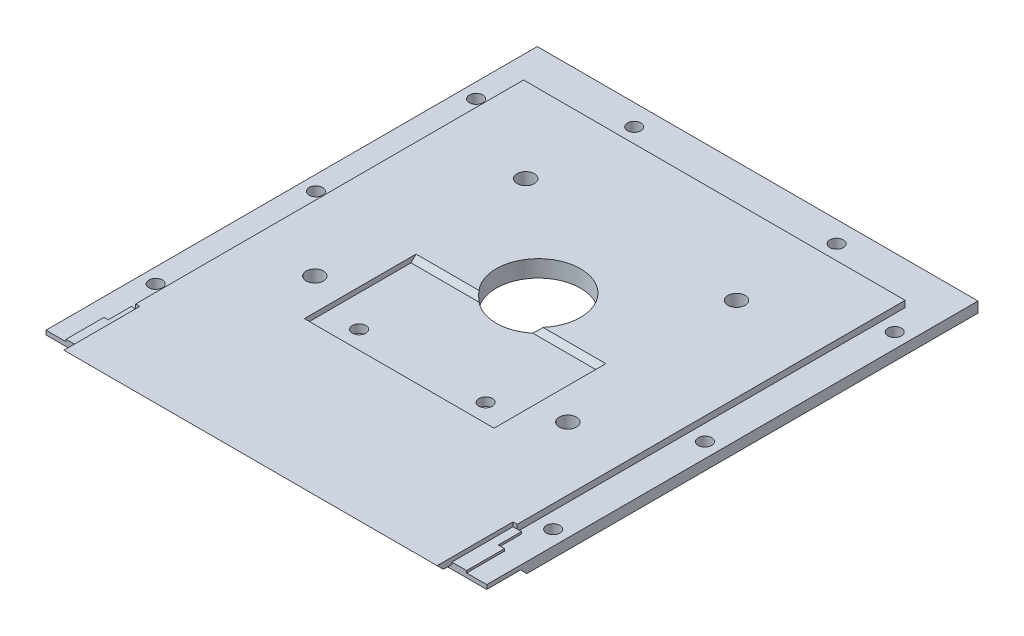
SolidWorks part; units mm, degrees
ref_plane "前视基准面" through (0, 0, 0) normal (0, 0, 1) x (1, 0, 0)
ref_plane "上视基准面" through (0, 0, 0) normal (0, 1, 0) x (1, 0, 0)
ref_plane "右视基准面" through (0, 0, 0) normal (1, 0, 0) x (0, 0, -1)
other "Configuration Table"
sketch "草图1" plane through (0, 0, 0) normal (0, 1, 0) x (1, 0, 0)
  line L1 (0, 0) -> (90.5, 0)
  line L2 (0, 0) -> (0, 97)
  line L3 (0, 97) -> (90.5, 97)
  line L4 (90.5, 0) -> (90.5, 97)
  dimension "D1" = 90.5
  dimension "D2" = 97
extrude "凸台-拉伸1" add sketch "草图1" along normal blind 2
sketch "草图2" plane through (0, 0, 0) normal (0, -1, 0) x (1, 0, 0)
  line L0 (45.25, 0) -> (45.25, -97) construction
  line L1 (0, 0) -> (90.5, 0) construction
  line L2 (90.5, -97) -> (0, -97) construction
  line L3 (-3.25, -13) -> (-3.25, -89) construction
  line L4 (-6.75, 17) -> (97.775, 17)
  line L5 (-6.75, 17) -> (-6.75, -107)
  line L6 (-6.75, -107) -> (97.775, -107)
  line L7 (97.775, 17) -> (97.775, -107)
  line L8 (94.275, -90.75) -> (94.275, -9.75) construction
  circle A0 centre (21.25, -102) radius 1.6
  circle A1 centre (69.25, -102) radius 1.6
  circle A2 centre (-3.25, -89) radius 1.6
  circle A3 centre (94.275, -90.75) radius 1.6
  circle A4 centre (-3.25, -13) radius 1.6
  circle A5 centre (-3.25, -51) radius 1.6
  circle A6 centre (94.275, -9.75) radius 1.6
  circle A7 centre (94.275, -45.75) radius 1.6
  dimension "D1" = 3.2
  dimension "D2" = 48
  dimension "D3" = 5
  dimension "D4" = 5
  dimension "D5" = 24.5
  dimension "D6" = 3.5
  dimension "D7" = 13
  dimension "D8" = 25.025
  dimension "D9" = 11.25
  dimension "D11" = 38
  dimension "D12" = 45
  dimension "D13" = 36
  dimension "D10" = 3.5
  dimension "D14" = 114
extrude "凸台-拉伸2" add sketch "草图2" along normal blind 2.5
sketch "草图3" plane through (0, 0, 0) normal (0, 1, 0) x (1, 0, 0)
  line L0 (0, 0) -> (90.5, 0) construction
  line L1 (1, 0) -> (89.5, 0)
  line L2 (1, 0) -> (1, -17)
  line L3 (1, -17) -> (89.5, -17)
  line L4 (89.5, 0) -> (89.5, -17)
  line L5 (97.775, -17) -> (-6.75, -17) construction
  line L6 (0, 97) -> (0, 0) construction
  line L7 (90.5, 0) -> (90.5, 97) construction
  dimension "D1" = 1
  dimension "D2" = 1
extrude "凸台-拉伸3" add sketch "草图3" along normal up to surface (2 mm away) up to face at (45.25, 2, -48.5)
sketch "草图4" plane through (0, 0, 0) normal (0, 1, 0) x (1, 0, 0)
  line L0 (0, 97) -> (0, 0) construction
  line L1 (1, 0) -> (0, 0)
  line L2 (1, 0) -> (1, 5)
  line L3 (1, 5) -> (0, 5)
  line L4 (0, 0) -> (0, 5)
  line L5 (90.5, 0) -> (90.5, 97) construction
  line L6 (89.5, 0) -> (90.5, 0)
  line L7 (89.5, 0) -> (89.5, 5)
  line L8 (89.5, 5) -> (90.5, 5)
  line L9 (90.5, 0) -> (90.5, 5)
  dimension "D1" = 5
extrude "切除-拉伸1" cut sketch "草图4" along normal up to surface (2 mm away) up to face at (45.25, 2, -20)
sketch "草图5" plane through (97.775, 0, 0) normal (1, 0, 0) x (0, 0, -1)
  line L0 (-8.5, -2.5) -> (-8.5, 0)
  line L1 (107, -2.5) -> (-17, -2.5) construction
  line L2 (107, 0) -> (-17, 0) construction
  line L4 (5, 2) -> (-17, 2) construction
  line L5 (-11.5, 2) -> (-17, 2)
  line L6 (-17, 2) -> (-17, -2.5)
  line L7 (-17, -2.5) -> (-8.5, -2.5)
  line L8 (-11.5, 2) -> (-9.5, 0)
  line L9 (-17, 0) -> (5, 0) construction
  line L10 (-9.5, 0) -> (-8.5, 0)
  dimension "D1" = 8.5
  dimension "D2" = 1
  dimension "D3" = 45
extrude "切除-拉伸2" cut sketch "草图5" against normal through all
sketch "草图6" plane through (0, 2, 0) normal (0, 1, 0) x (1, 0, 0)
  line L0 (45.5125, 107) -> (45.5125, 47) construction
  line L1 (68.0125, 22) -> (23.0125, 22)
  line L2 (68.0125, 22) -> (68.0125, 47)
  line L3 (68.0125, 47) -> (23.0125, 47)
  line L4 (23.0125, 22) -> (23.0125, 47)
  line L5 (-6.75, 107) -> (97.775, 107) construction
  line L7 (90.5, 97) -> (0, 97) construction
  dimension "D1" = 25
  dimension "D2" = 45
  dimension "D3" = 50
extrude "切除-拉伸3" cut sketch "草图6" against normal blind 1.7
sketch "草图7" plane through (0, 0.3, 0) normal (0, 1, 0) x (1, 0, 0)
  line L0 (23.0125, 27.5) -> (68.0125, 27.5) construction
  line L1 (23.0125, 47) -> (23.0125, 22) construction
  line L2 (68.0125, 22) -> (68.0125, 47) construction
  line L3 (23.0125, 22) -> (68.0125, 22) construction
  line L4 (45.5125, 47) -> (45.5125, 22) construction
  line L5 (68.0125, 47) -> (23.0125, 47) construction
  line L6 (23.0125, 22) -> (68.0125, 22) construction
  circle A0 centre (30.5125, 27.5) radius 1.6
  circle A1 centre (60.5125, 27.5) radius 1.6
  dimension "D2" = 30
  dimension "D3" = 3.2
  dimension "D1" = 5.5
extrude "切除-拉伸4" cut sketch "草图7" against normal up to next
chamfer "倒角1" distance 2 angle 45 1 edges at (45.5125, 2, -47)
sketch "草图8" plane through (0, 2, 0) normal (0, 1, 0) x (1, 0, 0)
  line L0 (45.5125, 107) -> (45.5125, -11.5) construction
  line L1 (-6.75, 107) -> (97.775, 107) construction
  line L3 (20.5125, 77) -> (70.5125, 77) construction
  line L4 (1, -11.5) -> (89.5, -11.5) construction
  line L5 (90.5, 97) -> (0, 97) construction
  circle A0 centre (20.5125, 77) radius 2.05
  circle A1 centre (70.5125, 77) radius 2.05
  circle A2 centre (15.5125, 32) radius 2.05
  circle A3 centre (75.5125, 32) radius 2.05
  dimension "D1" = 4.1
  dimension "D4" = 60
  dimension "D2" = 50
  dimension "D3" = 20
  dimension "D5" = 45
extrude "切除-拉伸5" cut sketch "草图8" against normal up to next
sketch "草图9" plane through (0, 2, 0) normal (0, 1, 0) x (1, 0, 0)
  line L0 (45.5125, 107) -> (45.5125, 55) construction
  line L1 (-6.75, 107) -> (97.775, 107) construction
  circle A0 centre (45.5125, 55) radius 10
  dimension "D1" = 20
  dimension "D2" = 52
extrude "切除-拉伸6" cut sketch "草图9" against normal up to next
sketch "草图10" plane through (0, -2.5, 0) normal (0, -1, 0) x (1, 0, 0)
  line L1 (27.7625, -25.9123) -> (27.7625, -29.0877)
  line L2 (27.7625, -29.0877) -> (30.5125, -30.6754)
  line L3 (30.5125, -30.6754) -> (33.2625, -29.0877)
  line L4 (33.2625, -29.0877) -> (33.2625, -25.9123)
  line L5 (33.2625, -25.9123) -> (30.5125, -24.3246)
  line L6 (30.5125, -24.3246) -> (27.7625, -25.9123)
  line L7 (57.7625, -25.9123) -> (57.7625, -29.0877)
  line L8 (57.7625, -29.0877) -> (60.5125, -30.6754)
  line L9 (60.5125, -30.6754) -> (63.2625, -29.0877)
  line L10 (63.2625, -29.0877) -> (63.2625, -25.9123)
  line L11 (63.2625, -25.9123) -> (60.5125, -24.3246)
  line L12 (60.5125, -24.3246) -> (57.7625, -25.9123)
  circle A0 centre (30.5125, -27.5) radius 2.75 construction
  circle A1 centre (60.5125, -27.5) radius 2.75 construction
  dimension "D1" = 5.5
extrude "切除-拉伸7" cut sketch "草图10" against normal blind 0.8
sketch "草图11" plane through (97.775, 0, 0) normal (1, 0, 0) x (0, 0, -1)
  line L0 (107, -2.5) -> (-8.5, -2.5) construction
  line L1 (-8.5, 0) -> (-2, 0)
  line L2 (-8.5, 0) -> (-8.5, -2.5)
  line L3 (-8.5, -2.5) -> (-2, -2.5)
  line L4 (-2, 0) -> (-2, -2.5)
  dimension "D1" = 6.5
extrude "切除-拉伸8" cut sketch "草图11" against normal up to next
chamfer "倒角2" distance 2 angle 45 1 edges at (45.5125, -2.5, 2)
sketch "草图12" plane through (0, 0, 0) normal (0, -1, 0) x (1, 0, 0)
  line L0 (1, 9.5) -> (89.5, 9.5) construction
  line L1 (-6.75, 0) -> (97.775, 0)
  line L2 (-6.75, 0) -> (-6.75, 9.5)
  line L3 (-6.75, 9.5) -> (97.775, 9.5)
  line L4 (97.775, 0) -> (97.775, 9.5)
  line L6 (97.775, 0) -> (-6.75, 0) construction
extrude "凸台-拉伸4" add sketch "草图12" along normal blind 1
sketch "草图13" plane through (0, 0, 0) normal (0, 1, 0) x (1, 0, 0)
  line L0 (1, -11.5) -> (1, 5) construction
  line L1 (1, 5) -> (-1, 5)
  line L2 (1, 5) -> (1, -9.5)
  line L3 (1, -9.5) -> (-1, -9.5)
  line L4 (-1, 5) -> (-1, -9.5)
  line L5 (89.5, 5) -> (91.5, 5)
  line L6 (89.5, 5) -> (89.5, -9.5)
  line L7 (89.5, -9.5) -> (91.5, -9.5)
  line L8 (91.5, 5) -> (91.5, -9.5)
  line L9 (1, -9.5) -> (-6.75, -9.5) construction
  dimension "D1" = 2
  dimension "D2" = 2
extrude "凸台-拉伸5" add sketch "草图13" along normal blind 0.5
sketch "草图14" plane through (0, 0, 0) normal (0, 1, 0) x (1, 0, 0)
  line L0 (97.775, -9.5) -> (91.5, -9.5) construction
  line L1 (93, -9.5) -> (91.5, -9.5)
  line L2 (93, -9.5) -> (93, -0.5)
  line L3 (93, -0.5) -> (91.5, -0.5)
  line L4 (91.5, -9.5) -> (91.5, -0.5)
  line L6 (-1, -9.5) -> (-6.75, -9.5) construction
  line L7 (-2, -9.5) -> (-1, -9.5)
  line L8 (-2, -9.5) -> (-2, -0.5)
  line L9 (-2, -0.5) -> (-1, -0.5)
  line L10 (-1, -9.5) -> (-1, -0.5)
  line L11 (-1, 5) -> (-1, -9.5) construction
  line L12 (91.5, -9.5) -> (91.5, 5) construction
  dimension "D1" = 1
  dimension "D2" = 1.5
  dimension "D3" = 9
extrude "凸台-拉伸6" add sketch "草图14" along normal up to surface (0.5 mm away) up to face at (0, 0.5, 0.8)
sketch "草图15" plane through (0, -4.75, 4.75) normal (0, -0.7071, 0.7071) x (1, 0, 0)
  line L4 (89.5, 9.5459) -> (1, 9.5459)
  line L5 (1, 9.5459) -> (1, 6.7175)
  line L6 (1, 6.7175) -> (89.5, 6.7175)
  line L7 (89.5, 6.7175) -> (89.5, 9.5459)
  line L8 (89.5, 9.5459) -> (1, 9.5459)
  line L9 (1, 9.5459) -> (1, 6.7175)
  line L10 (1, 6.7175) -> (89.5, 6.7175)
  line L11 (89.5, 6.7175) -> (89.5, 9.5459)
  dimension "D1" = 0
extrude "凸台-拉伸7" add sketch "草图15" along direction (0, 0, 1) on the side of the normal blind 2
sketch "草图16" plane through (0, 2, 0) normal (0, 1, 0) x (1, 0, 0)
  line L8 (1, 5) -> (1, -13.5)
  line L9 (1, -13.5) -> (89.5, -13.5)
  line L10 (89.5, -13.5) -> (89.5, 5)
  line L11 (89.5, 5) -> (90.5, 5)
  line L12 (90.5, 5) -> (90.5, 97)
  line L13 (90.5, 97) -> (0, 97)
  line L14 (0, 97) -> (0, 5)
  line L15 (0, 5) -> (1, 5)
  line L16 (1, 5) -> (1, -13.5)
  line L17 (1, -13.5) -> (89.5, -13.5)
  line L18 (89.5, -13.5) -> (89.5, 5)
  line L19 (89.5, 5) -> (90.5, 5)
  line L20 (90.5, 5) -> (90.5, 97)
  line L21 (90.5, 97) -> (0, 97)
  line L22 (0, 97) -> (0, 5)
  line L23 (0, 5) -> (1, 5)
  dimension "D1" = 0
extrude "切除-拉伸9" cut sketch "草图16" against normal blind 0.5
